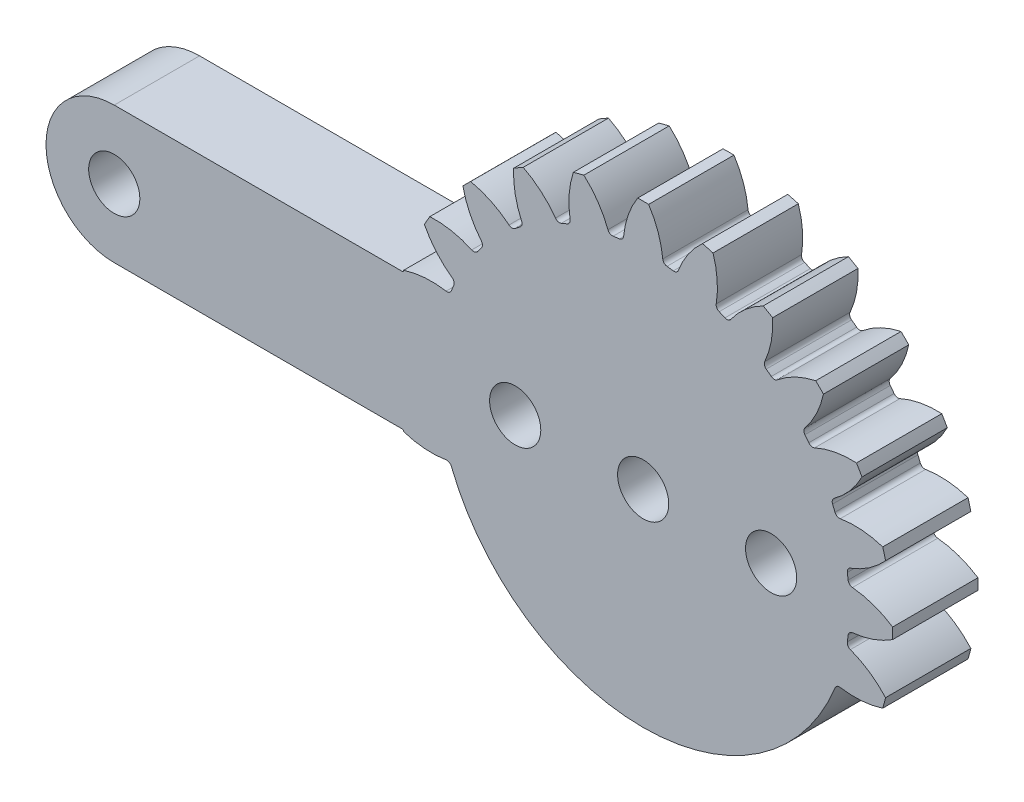
SolidWorks part; units mm, degrees
material "아크릴(내충격성)"
ref_plane "정면" through (0, 0, 0) normal (0, 0, 1) x (1, 0, 0)
ref_plane "윗면" through (0, 0, 0) normal (0, 1, 0) x (1, 0, 0)
ref_plane "우측면" through (0, 0, 0) normal (1, 0, 0) x (0, 0, -1)
sketch "스케치1" plane through (0, 0, 0) normal (0, 0, 1) x (1, 0, 0)
  line L0 (0, 17.8552) -> (0, -21.2428) construction
  line L1 (0.8831, 13.4711) -> (0.8831, -21.2428) construction
  line L2 (0.3206, 14.6215) -> (0.3206, -21.2428) construction
  line L3 (1.1644, 12.0376) -> (1.1644, -21.2428) construction
  line L4 (1.1644, 17.8552) -> (1.1644, -21.2428) construction
  line L5 (0.8831, 17.8552) -> (0.8831, -21.2428) construction
  line L6 (0.3206, 17.8552) -> (0.3206, -21.2428) construction
  circle A0 centre (0, 0) radius 13.5 construction
  circle A1 centre (0, 0) radius 14.625
  circle A2 centre (0, 0) radius 12.0938
  arc A3 (1.1644, 12.0376) -> (0.3206, 14.6215) centre (-4.0938, 11.7503) ccw
  arc A4 (-1.1644, 12.0376) -> (-0.3206, 14.6215) centre (4.0938, 11.7503) cw
  circle A5 centre (0, 0) radius 1.5
  point P17 (-0.8831, 13.4711)
  dimension "D1" = 27
  dimension "D2" = 29.25
  dimension "D3" = 24.1875
  dimension "D7" = 3
  dimension "D6" = 0.2812
  dimension "D4" = 0.8831
  dimension "D5" = 0.5625
extrude "보스-돌출2" add sketch "스케치1" along normal blind 5 contours A2 A3 region at (8.7005, 7.8996, 0)
extrude "보스-돌출3" add sketch "스케치1<4>" along normal blind 5 contours A4 A2 A3 A1 region at (0, 13.145, 0)
sketch "스케치1<4>" plane through (0, 0, 0) normal (0, 0, 1) x (1, 0, 0) same geometry as "스케치1"
fillet "필렛2" radius 0.2812 2 edges at (-1.1644, 12.0376, 2.5) (1.1644, 12.0376, 2.5)
pattern_circular "원형 패턴1" count 24 over 360 about axis through (0, 0, 5) along (0, 0, -1) of "보스-돌출3", "필렛2" reverse direction yes
sketch "스케치2" plane through (0, 0, 5) normal (0, 0, 1) x (1, 0, 0)
  line L0 (0, 0) -> (-31, 0) construction
  line L1 (0, -4) -> (-31, -4)
  line L2 (0, 4) -> (-31, 4)
  arc A0 (0, -4) -> (0, 4) centre (0, 0) ccw
  arc A1 (-31, 4) -> (-31, -4) centre (-31, 0) ccw
  circle A2 centre (-31, 0) radius 1.5
  circle A4 centre (0, 0) radius 1.5 construction
  circle A5 centre (0, 0) radius 1.5
  point P3 (-15.5, 0)
  dimension "D2" = 3
  dimension "D1" = 31
  dimension "D3" = 8
extrude "보스-돌출4" add sketch "스케치2" against normal up to surface (5 mm away) up to face at (1.5, 0, 0)
sketch "스케치3" plane through (0, 0, 5) normal (0, 0, 1) x (1, 0, 0)
  arc A1 (-11.1732, -4.6281) -> (11.1576, -4.6655) centre (0, 0) ccw
  arc A2 (-11.2428, -4.4562) -> (-11.1009, -4.7989) centre (0, 0) ccw construction
extrude "컷-돌출-얇게1" cut sketch "스케치3" against normal blind 5 and the other way through all thin contours A1 thin type one direction wall 10
sketch "스케치4" plane through (0, 0, 5) normal (0, 0, 1) x (1, 0, 0)
  line L0 (-7.5, 0) -> (7.5, 0) construction
  circle A0 centre (7.5, 0) radius 1.5
  circle A1 centre (-7.5, 0) radius 1.5
  dimension "D1" = 3
  dimension "D2" = 15
extrude "컷-돌출2" cut sketch "스케치4" against normal up to next
